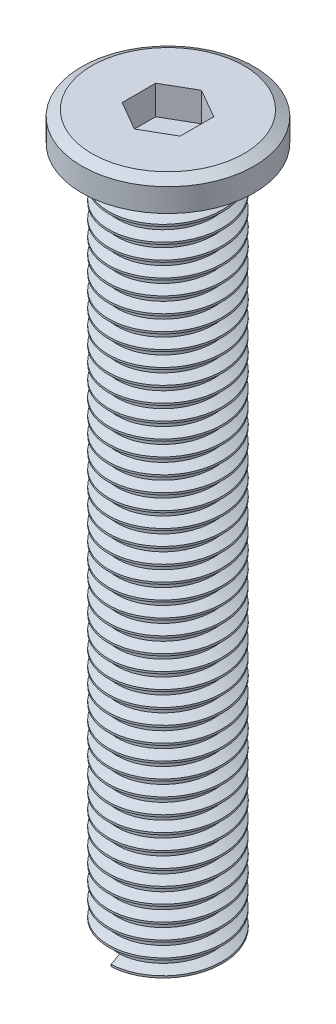
SolidWorks part; units mm, degrees
ref_plane "Front Plane" through (0, 0, 0) normal (0, 0, 1) x (1, 0, 0)
ref_plane "Top Plane" through (0, 0, 0) normal (0, 1, 0) x (1, 0, 0)
ref_plane "Right Plane" through (0, 0, 0) normal (1, 0, 0) x (0, 0, -1)
sketch "Sketch1" plane through (0, 0, 0) normal (0, 1, 0) x (1, 0, 0)
  circle A0 centre (0, 0) radius 4.45
  dimension "D1" = 8.9
extrude "Boss-Extrude1" add sketch "Sketch1" along normal blind 1.5
chamfer "Chamfer2" distance 0.3 angle 60 1 edges at (0, 1.5, 4.45)
sketch "Sketch8" plane through (0, 1.5, 0) normal (0, 1, 0) x (1, 0, 0)
  line L1 (0, 1.7321) -> (-1.5, 0.866)
  line L2 (-1.5, 0.866) -> (-1.5, -0.866)
  line L3 (-1.5, -0.866) -> (0, -1.7321)
  line L4 (0, -1.7321) -> (1.5, -0.866)
  line L5 (1.5, -0.866) -> (1.5, 0.866)
  line L6 (1.5, 0.866) -> (0, 1.7321)
  circle A0 centre (0, 0) radius 1.5 construction
  dimension "D1" = 3
  dimension "D2" = 1.5
extrude "Cut-Extrude1" cut sketch "Sketch8" against normal blind 3
sketch "Sketch3" plane through (0, 0, 0) normal (0, -1, 0) x (1, 0, 0)
  circle A0 centre (0, 0) radius 2.5
  dimension "D1" = 5
extrude "Boss-Extrude2" add sketch "Sketch3" along normal blind 35
thread "Thread1" pitch 0.8 start angle 0, offset 0, length 0, pitch 0.8, diameter 5
ref_plane "Plane2" through (-2.5, 0, 0) normal (0, 0, 1) x (-1, 0, 0)
sketch "Thread Profile2" plane through (-2.5, 0, 0) normal (0, 0, 1) x (-1, 0, 0)
  line L0 (0, 0) -> (0, 0.8) construction
  line L1 (0, 0) -> (0.433, 0.25)
  line L2 (0.433, 0.25) -> (0.433, 0.35)
  line L3 (0.433, 0.35) -> (0, 0.6)
  line L4 (0.433, 0.3) -> (0, 0.3) construction
  line L11 (0, 0) -> (0, 0.6)
  point P2 (0, 0)
  dimension "Pitch" = 0.8
  dimension "Profile_Angle" = 60
  dimension "Profile_Land" = 0.1
  dimension "Profile_Height" = 0.433
